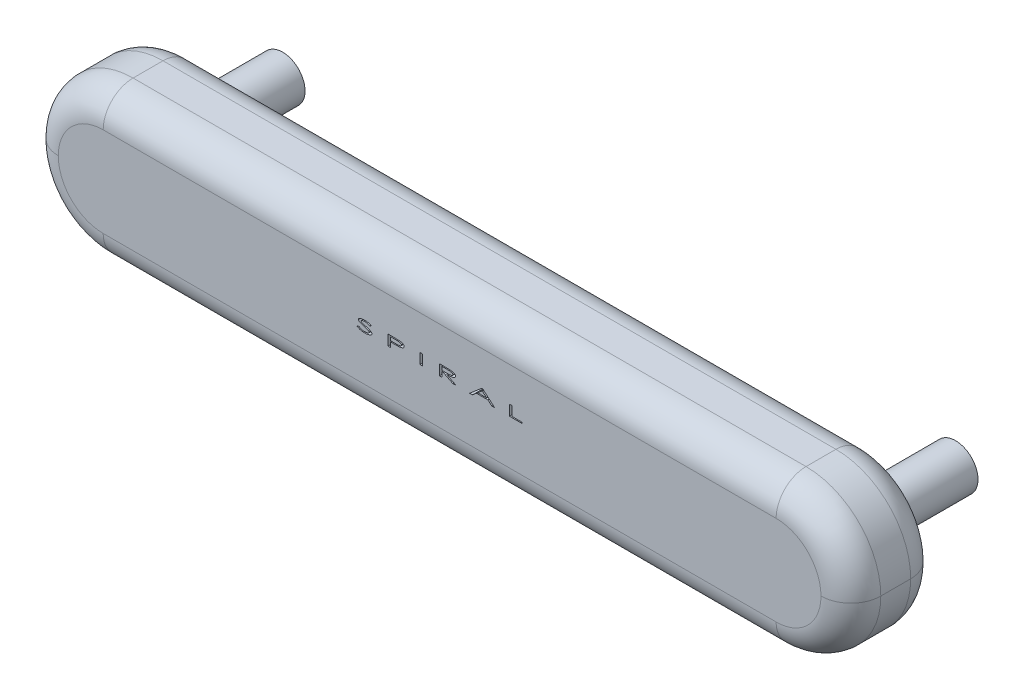
SolidWorks part; units mm, degrees
ref_plane "Alzado" through (0, 0, 0) normal (0, 0, 1) x (1, 0, 0)
ref_plane "Planta" through (0, 0, 0) normal (0, 1, 0) x (1, 0, 0)
ref_plane "Vista lateral" through (0, 0, 0) normal (1, 0, 0) x (0, 0, -1)
sketch "Croquis1" plane through (0, 0, 0) normal (0, 0, 1) x (1, 0, 0)
  line L1 (0, 0) -> (275, 0)
  line L2 (0, 0) -> (0, 50)
  line L3 (0, 50) -> (275, 50)
  line L4 (275, 0) -> (275, 50)
  circle A0 centre (25, 25) radius 7.5
  circle A1 centre (250, 25) radius 7.5
extrude "Saliente-Extruir1" add sketch "Croquis1" along normal blind 30 contours L3 L4 L1 L2
fillet "Redondeo1" radius 25 4 edges at (0, 0, 15) (275, 0, 15) (275, 50, 15) (0, 50, 15)
extrude "Saliente-Extruir2" add sketch "Croquis1<3>" against normal blind 30 contours A0
sketch "Croquis1<3>" plane through (0, 0, 0) normal (0, 0, 1) x (1, 0, 0) same geometry as "Croquis1"
extrude "Saliente-Extruir3" add sketch "Croquis1<4>" against normal blind 30 contours A1
sketch "Croquis1<4>" plane through (0, 0, 0) normal (0, 0, 1) x (1, 0, 0) same geometry as "Croquis1"
fillet "Redondeo2" radius 10 12 edges at (137.5, 0, 30) (267.6777, 42.6777, 30) (267.6777, 7.3223, 30) (267.6777, 42.6777, 0) (267.6777, 7.3223, 0) (7.3223, 7.3223, 0) (7.3223, 7.3223, 30) (7.3223, 42.6777, 30) (7.3223, 42.6777, 0) (137.5, 0, 0) (137.5, 50, 0) (137.5, 50, 30)
sketch "Croquis2" plane through (0, 0, 30) normal (0, 0, 1) x (1, 0, 0)
  line L0 (10, 25) -> (265, 25) construction
  arc A0 (250, 10) -> (265, 25) centre (250, 25) ccw construction
  text T0 "SPIRAL" font "Century Gothic" height 3.5
extrude "Cortar-Extruir1" cut sketch "Croquis2" against normal blind 5
